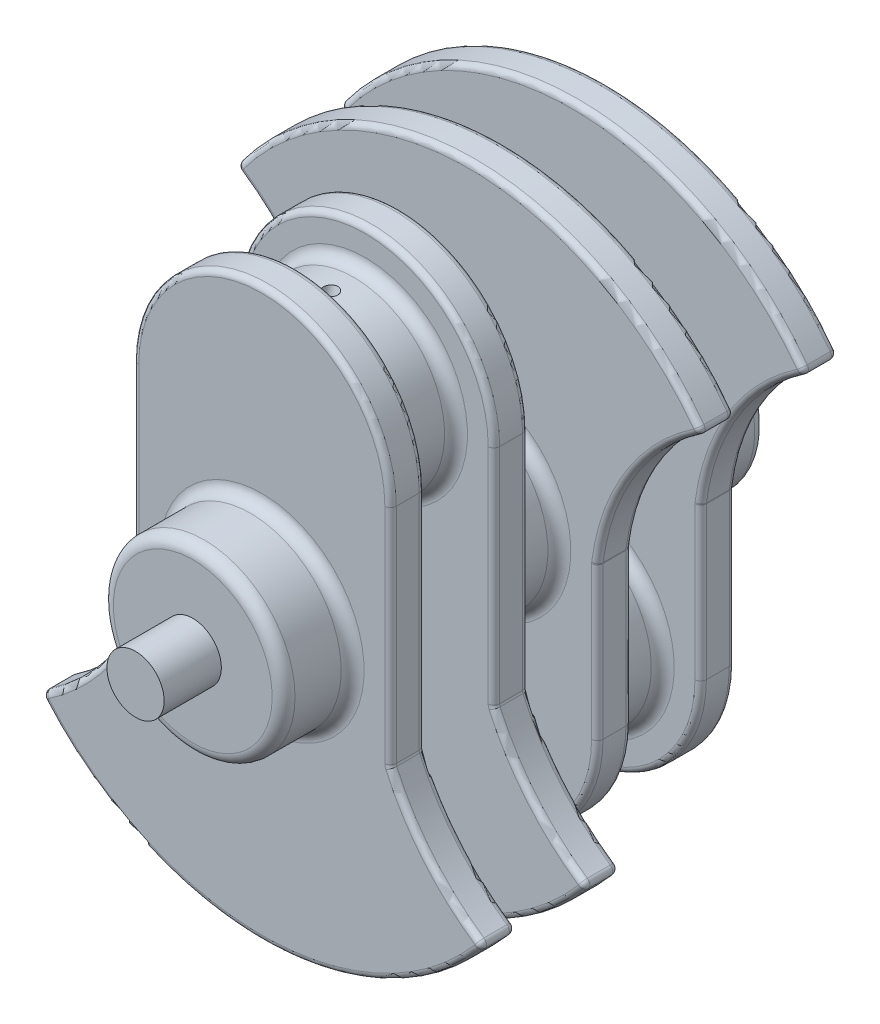
SolidWorks part; units mm, degrees
material "AISI 4340 Steel, normalized"
ref_plane "Front Plane" through (0, 0, 0) normal (0, 0, 1) x (1, 0, 0)
ref_plane "Top Plane" through (0, 0, 0) normal (0, 1, 0) x (1, 0, 0)
ref_plane "Right Plane" through (0, 0, 0) normal (1, 0, 0) x (0, 0, -1)
sketch "Sketch1" plane through (0, 0, 0) normal (0, 0, 1) x (1, 0, 0)
  circle A0 centre (0, 0) radius 31.75
  dimension "D1" = 31.75
extrude "Boss-Extrude1" add sketch "Sketch1" along normal blind 24.13
sketch "Sketch8" plane through (0, 0, 0) normal (0, 0, -1) x (-1, 0, 0)
  line L0 (-45, 53.333) -> (-45, -24.9419)
  line L1 (45, 53.333) -> (45, -24.9419)
  arc A0 (45, 53.333) -> (-45, 53.333) centre (0, 53.333) ccw
  arc A5 (-77.4745, -63.2274) -> (77.4745, -63.2274) centre (0, 0) ccw
  arc A6 (-45, -24.9419) -> (-77.4745, -63.2274) centre (-125, 10) cw
  arc A7 (45, -24.9419) -> (77.4745, -63.2274) centre (125, 10) ccw
  dimension "D1" = 45
  dimension "D2" = 100
  dimension "D3" = 53.333
  dimension "D5" = 10
  dimension "D6" = 125
extrude "Boss-Extrude5" add sketch "Sketch8" along normal blind 12
sketch "Sketch2" plane through (0, 0, 24.13) normal (0, 0, 1) x (1, 0, 0)
  circle A0 centre (0, 0) radius 10
  dimension "D1" = 10
extrude "Boss-Extrude2" add sketch "Sketch2" along normal blind 20
sketch "Sketch9" plane through (0, 0, -12) normal (0, 0, -1) x (-1, 0, 0)
  circle A0 centre (0, 53.333) radius 31.75
  dimension "D2" = 31.75
  dimension "D1" = 53.333
extrude "Boss-Extrude6" add sketch "Sketch9" along normal blind 24.13
ref_plane "Plane4" through (0, 0, -72.26) normal (0, 0, -1) x (-1, 0, 0)
sketch "Sketch10" plane through (0, 0, -36.13) normal (0, 0, -1) x (-1, 0, 0)
  line L0 (-45, -53.333) -> (-45, 0)
  line L1 (45, -53.333) -> (45, 0)
  arc A0 (-45, -53.333) -> (45, -53.333) centre (0, -53.333) ccw
  arc A1 (-45, 0) -> (-81.5321, 57.901) centre (-125, -10) ccw
  arc A2 (45, 0) -> (81.5321, 57.901) centre (125, -10) cw
  arc A3 (-81.5321, 57.901) -> (81.5321, 57.901) centre (0, 0) cw
  dimension "D1" = 45
  dimension "D5" = 10
  dimension "D3" = 100
  dimension "D2" = 53.333
  dimension "D4" = 125
extrude "Boss-Extrude7" add sketch "Sketch10" along normal blind 12 from surface starting at plane "Plane4"
ref_plane "Plane3" through (0, 0, -108.39) normal (0, 0, -1) x (-1, 0, 0)
sketch "Sketch12" plane through (0, 0, -108.39) normal (0, 0, -1) x (-1, 0, 0)
  line L2 (45, -53.333) -> (45, 0)
  line L3 (45, -53.333) -> (45, 0)
  line L4 (-45, 0) -> (-45, -53.333)
  line L5 (-45, 0) -> (-45, -53.333)
  arc A12 (-45, -53.333) -> (45, -53.333) centre (0, -53.333) ccw
  arc A13 (81.5321, 57.901) -> (45, 0) centre (125, -10) ccw
  arc A14 (81.5321, 57.901) -> (-81.5321, 57.901) centre (0, 0) ccw
  arc A15 (-45, 0) -> (-81.5321, 57.901) centre (-125, -10) ccw
  arc A16 (-45, -53.333) -> (45, -53.333) centre (0, -53.333) ccw
  arc A17 (81.5321, 57.901) -> (45, 0) centre (125, -10) ccw
  arc A18 (81.5321, 57.901) -> (-81.5321, 57.901) centre (0, 0) ccw
  arc A19 (-45, 0) -> (-81.5321, 57.901) centre (-125, -10) ccw
  dimension "D1" = 0
extrude "Boss-Extrude8" add sketch "Sketch12" along normal blind 12
sketch "Sketch14" plane through (0, 0, -84.26) normal (0, 0, -1) x (-1, 0, 0)
  circle A0 centre (0, -53.333) radius 31.75
  dimension "D2" = 31.75
  dimension "D1" = 53.333
extrude "Boss-Extrude9" add sketch "Sketch14" along normal up to next
sketch "Sketch15" plane through (0, 0, -120.39) normal (0, 0, -1) x (-1, 0, 0)
  circle A1 centre (0, 0) radius 31.75
  circle A2 centre (0, 0) radius 31.75
  dimension "D1" = 0
extrude "Boss-Extrude10" add sketch "Sketch15" along normal blind 24.13
sketch "Sketch16" plane through (0, 0, -144.52) normal (0, 0, -1) x (-1, 0, 0)
  circle A1 centre (0, 0) radius 10
  circle A2 centre (0, 0) radius 10
  dimension "D1" = 0
extrude "Boss-Extrude11" add sketch "Sketch16" along normal blind 20
sketch "Sketch18" plane through (0, 0, -36.13) normal (0, 0, -1) x (-1, 0, 0)
  line L2 (-45, 53.333) -> (-45, -24.9419)
  line L3 (-45, 53.333) -> (-45, -24.9419)
  line L4 (45, -24.9419) -> (45, 53.333)
  line L5 (45, -24.9419) -> (45, 53.333)
  arc A4 (45, 53.333) -> (-45, 53.333) centre (0, 53.333) ccw
  arc A5 (-77.4745, -63.2274) -> (-45, -24.9419) centre (-125, 10) ccw
  arc A6 (-77.4745, -63.2274) -> (77.4745, -63.2274) centre (0, 0) ccw
  arc A7 (45, -24.9419) -> (77.4745, -63.2274) centre (125, 10) ccw
  arc A8 (45, 53.333) -> (-45, 53.333) centre (0, 53.333) ccw
  arc A9 (-77.4745, -63.2274) -> (-45, -24.9419) centre (-125, 10) ccw
  arc A10 (-77.4745, -63.2274) -> (77.4745, -63.2274) centre (0, 0) ccw
  arc A11 (45, -24.9419) -> (77.4745, -63.2274) centre (125, 10) ccw
  dimension "D1" = 0
extrude "Boss-Extrude12" add sketch "Sketch18" along normal blind 12
sketch "Sketch19" plane through (0, 0, -48.13) normal (0, 0, -1) x (-1, 0, 0)
  circle A1 centre (0, 0) radius 31.75
  circle A2 centre (0, 0) radius 31.75
  dimension "D1" = 0
extrude "Boss-Extrude13" add sketch "Sketch19" along normal up to next
fillet "Fillet1" radius 2 32 edges at (0, -100, -36.13) (-58.4257, -46.4694, -36.13) (-45, 14.1956, -36.13) (45, 14.1956, -36.13) (58.4257, -46.4694, -36.13) (0, -100, -48.13) (-58.4257, -46.4694, -48.13) (-45, 14.1956, -48.13) (0, 98.333, -48.13) (45, 14.1956, -48.13) (58.4257, -46.4694, -48.13) (77.4745, -63.2274, -42.13) (45, -24.9419, -42.13) (-45, -24.9419, -42.13) (-77.4745, -63.2274, -42.13) (0, 98.333, -36.13) (45, 14.1956, 0) (58.4257, -46.4694, 0) (0, -100, 0) (-58.4257, -46.4694, 0) (-45, 14.1956, 0) (0, 98.333, -12) (45, 14.1956, -12) (58.4257, -46.4694, -12) (0, -100, -12) (-58.4257, -46.4694, -12) (-45, 14.1956, -12) (-45, -24.9419, -6) (-77.4745, -63.2274, -6) (77.4745, -63.2274, -6) (45, -24.9419, -6) (0, 98.333, 0)
fillet "Fillet2" radius 2 16 edges at (0, 100, -108.39) (56.8149, 33.0208, -108.39) (45, -26.6665, -108.39) (0, -98.333, -108.39) (-45, -26.6665, -108.39) (-56.8149, 33.0208, -108.39) (56.8149, 33.0208, -120.39) (45, -26.6665, -120.39) (0, -98.333, -120.39) (-45, -26.6665, -120.39) (-56.8149, 33.0208, -120.39) (-81.5321, 57.901, -114.39) (-45, 0, -114.39) (45, 0, -114.39) (81.5321, 57.901, -114.39) (0, 100, -120.39)
fillet "Fillet3" radius 2 16 edges at (45, -26.6665, -72.26) (56.8149, 33.0208, -72.26) (0, 100, -72.26) (-56.8149, 33.0208, -72.26) (-45, -26.6665, -72.26) (0, -98.333, -72.26) (45, -26.6665, -84.26) (56.8149, 33.0208, -84.26) (-56.8149, 33.0208, -84.26) (-45, -26.6665, -84.26) (0, -98.333, -84.26) (45, 0, -78.26) (81.5321, 57.901, -78.26) (-81.5321, 57.901, -78.26) (-45, 0, -78.26) (0, 100, -84.26)
fillet "Fillet5" radius 4 2 edges at (31.75, 0, 24.13) (31.75, 0, 0)
fillet "Fillet6" radius 4 2 edges at (-31.75, 0, -120.39) (-31.75, 0, -144.52)
ref_plane "Plane5" through (0, 31.75, 0) normal (0, 1, 0) x (1, 0, 0)
sketch "Sketch20" plane through (0, 0, 0) normal (1, 0, 0) x (0, 0, -1)
  line L1 (84.26, -85.083) -> (84.26, -21.583)
  line L2 (84.26, -85.083) -> (84.26, -21.583)
  dimension "D1" = 0
ref_plane "Plane6" through (0, -85.083, 0) normal (0, 1, 0) x (1, 0, 0)
sketch "Sketch21" plane through (0, 31.75, 0) normal (0, 1, 0) x (1, 0, 0)
  line L2 (-31.75, 140.52) -> (31.75, 140.52) construction
  line L3 (-31.75, 140.52) -> (-31.75, 124.39) construction
  line L4 (-31.75, 124.39) -> (31.75, 124.39) construction
  line L5 (31.75, 140.52) -> (31.75, 124.39) construction
  circle A0 centre (0, 132.455) radius 2.5
  point P10 (0, 140.52)
  point P11 (31.75, 132.455)
  dimension "D1" = 5
sketch "Sketch27" plane through (0, 0, 0) normal (0, 0, 1) x (1, 0, 0)
  line L0 (0, 85.083) -> (0, -31.75) construction
  circle A1 centre (0, 53.333) radius 31.75
  circle A2 centre (0, 53.333) radius 31.75 construction
  circle A3 centre (0, 0) radius 31.75
  circle A4 centre (0, 0) radius 31.75 construction
  dimension "D1" = 0
  dimension "D2" = 0
ref_plane "Plane8" through (0, 85.083, 0) normal (0, -1, 0) x (-1, 0, 0)
ref_plane "Plane9" through (0, -31.75, 0) normal (0, -1, 0) x (-1, 0, 0)
sketch "Sketch28" plane through (0, -31.75, 0) normal (0, -1, 0) x (-1, 0, 0)
  line L1 (-31.75, -4) -> (31.75, -4) construction
  line L2 (-31.75, -4) -> (-31.75, -20.13) construction
  line L3 (-31.75, -20.13) -> (31.75, -20.13) construction
  line L4 (31.75, -4) -> (31.75, -20.13) construction
  line L5 (-31.75, -4) -> (31.75, -20.13) construction
  line L6 (-31.75, -20.13) -> (31.75, -4) construction
  circle A0 centre (0, -12.065) radius 2.5
  point P4 (0, -12.065)
  dimension "D1" = 5
sketch "Sketch29" plane through (0, 85.083, 0) normal (0, -1, 0) x (-1, 0, 0)
  line L1 (31.75, 36.13) -> (-31.75, 36.13) construction
  line L2 (31.75, 36.13) -> (31.75, 12) construction
  line L3 (31.75, 12) -> (-31.75, 12) construction
  line L4 (-31.75, 36.13) -> (-31.75, 12) construction
  line L5 (31.75, 36.13) -> (-31.75, 12) construction
  line L6 (31.75, 12) -> (-31.75, 36.13) construction
  circle A0 centre (0, 24.065) radius 2.5
  point P4 (0, 24.065)
sketch "Sketch31" plane through (0, 0, 0) normal (1, 0, 0) x (0, 0, -1)
  line L0 (24.065, 85.083) -> (-12.065, -31.75) construction
ref_plane "Plane10" through (0, 85.083, -24.065) normal (0, -0.9554, 0.2954) x (-1, 0, 0)
ref_plane "Plane11" through (0, -31.75, 12.065) normal (0, -0.9554, 0.2954) x (-1, 0, 0)
combine bodies "Combine1" operation type add bodies to combine 119 109 117
fillet "Fillet7" radius 4 6 edges at (-31.75, 53.333, -36.13) (-31.75, 53.333, -12) (-31.75, 0, -48.13) (-31.75, 0, -72.26) (-31.75, -53.333, -108.39) (-31.75, -53.333, -84.26)
sketch "Sketch39" plane through (0, -85.083, 0) normal (0, 1, 0) x (1, 0, 0)
  line L1 (31.75, 104.39) -> (-31.75, 104.39) construction
  line L2 (31.75, 104.39) -> (31.75, 88.26) construction
  line L3 (31.75, 88.26) -> (-31.75, 88.26) construction
  line L4 (-31.75, 104.39) -> (-31.75, 88.26) construction
  line L5 (31.75, 104.39) -> (-31.75, 88.26) construction
  line L6 (31.75, 88.26) -> (-31.75, 104.39) construction
  point P4 (0, 96.325)
sketch "Sketch40" plane through (0, 0, 0) normal (1, 0, 0) x (0, 0, -1)
  line L0 (132.455, 31.75) -> (96.325, -85.083) construction
  line L1 (140.52, 31.75) -> (124.39, 31.75) construction
ref_plane "Plane12" through (0, 31.75, -132.455) normal (0, -0.9554, 0.2954) x (-1, 0, 0)
ref_plane "Plane13" through (0, -85.083, -96.325) normal (0, -0.9554, 0.2954) x (-1, 0, 0)
sketch "Sketch47" plane through (0, 85.083, -24.065) normal (0, -0.9554, 0.2954) x (-1, 0, 0)
  ellipse E0 centre (0, 0) end of major axis (2.5, 0) minor radius 2.3884 construction
  ellipse E1 centre (0, 0) end of major axis (2.5, 0) minor radius 2.3884
extrude "Cut-Extrude1" cut sketch "Sketch47" along normal through all
sketch "Sketch48" plane through (0, -31.75, 12.065) normal (0, -0.9554, 0.2954) x (-1, 0, 0)
  ellipse E0 centre (0, 0) end of major axis (2.5, 0) minor radius 2.3884 construction
  ellipse E1 centre (0, 0) end of major axis (2.5, 0) minor radius 2.3884
extrude "Cut-Extrude2" cut sketch "Sketch48" against normal through all
sketch "Sketch49" plane through (0, -85.083, -96.325) normal (0, -0.9554, 0.2954) x (-1, 0, 0)
  circle A0 centre (0, 0) radius 2.5
  dimension "D1" = 5
extrude "Cut-Extrude3" cut sketch "Sketch49" against normal through all
sketch "Sketch50" plane through (0, 31.75, -132.455) normal (0, -0.9554, 0.2954) x (-1, 0, 0)
  circle A0 centre (0, 0) radius 2.5 construction
  circle A1 centre (0, 0) radius 2.5
extrude "Cut-Extrude4" cut sketch "Sketch50" along normal through all
equation "\"CR\"= 53.333mm'Crank Radius"
equation "\"D1@Sketch9\"=\"CR\""
equation "\"D1@Sketch14\"=\"CR\""
equation "\"JR\"= 31.75mm'Journal Radius"
equation "\"D1@Sketch1\"=\"JR\""
equation "\"D2@Sketch9\"=\"JR\""
equation "\"D2@Sketch14\"=\"JR\""
equation "\"LT\" = 12mm'Lobe Thickness"
equation "\"D1@Boss-Extrude5\"=\"LT\""
equation "\"D1@Boss-Extrude7\"=\"LT\""
equation "\"D1@Boss-Extrude8\"=\"LT\""
equation "\"D1@Boss-Extrude12\"=\"LT\""
equation "\"D3@Sketch8\"=\"CR\""
equation "\"D2@Sketch10\"=\"CR\""
equation "\"JL\"= 24.13mm'Journal Length"
equation "\"D1@Boss-Extrude1\"=\"JL\""
equation "\"D1@Boss-Extrude6\"=\"JL\""
equation "\"D1@Boss-Extrude10\"=\"JL\""
equation "\"LHD\"= 5mm'Lubrication Hole Diameter"
equation "\"D1@Sketch29\"=\"LHD\""
